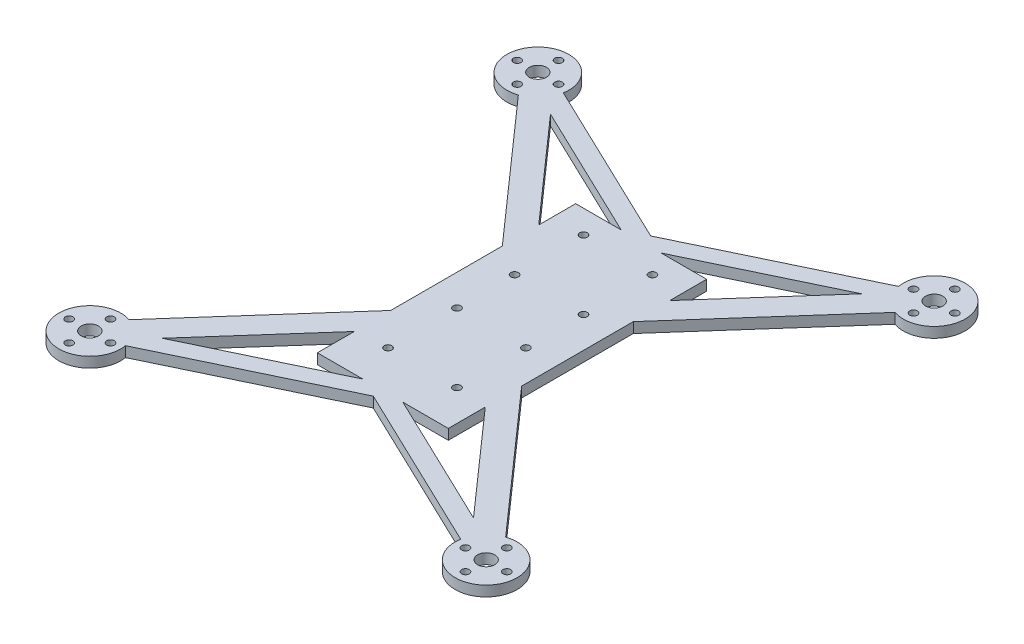
SolidWorks part; units mm, degrees
ref_plane "Front Plane" through (0, 0, 0) normal (0, 0, 1) x (1, 0, 0)
ref_plane "Top Plane" through (0, 0, 0) normal (0, 1, 0) x (1, 0, 0)
ref_plane "Right Plane" through (0, 0, 0) normal (1, 0, 0) x (0, 0, -1)
sketch "Sketch1" plane through (0, 0, 0) normal (0, 1, 0) x (1, 0, 0)
  line L0 (0, 37.475) -> (0, -37.475) construction
  line L1 (19, 37.475) -> (-19, 37.475)
  line L2 (19, 37.475) -> (19, -37.475)
  line L3 (19, -37.475) -> (-19, -37.475)
  line L4 (-19, 37.475) -> (-19, -37.475)
  line L5 (19, 37.475) -> (-19, -37.475) construction
  line L6 (19, -37.475) -> (-19, 37.475) construction
  line L7 (-19, 16.1958) -> (-54.6277, 56.4706)
  line L8 (57.5, -65) -> (-57.5, -65)
  line L9 (57.5, -65) -> (57.5, 65)
  line L10 (57.5, 65) -> (-57.5, 65)
  line L11 (-57.5, -65) -> (-57.5, 65)
  line L12 (57.5, -65) -> (-57.5, 65) construction
  line L13 (57.5, 65) -> (-57.5, -65) construction
  line L14 (-19, 16.1958) -> (-13.757, 20.8338)
  line L15 (-54.6277, 56.4706) -> (-49.3847, 61.1087)
  line L16 (-13.757, 20.8338) -> (-49.3847, 61.1087)
  line L17 (-19, 16.1958) -> (-49.3847, 61.1087) construction
  line L18 (-54.6277, 56.4706) -> (-13.757, 20.8338) construction
  line L19 (-57.5, 65) -> (0, 37.475) construction
  line L20 (-10, 30.75) -> (10, 30.75)
  line L21 (-10, 30.75) -> (-10, 10.75)
  line L22 (-10, 10.75) -> (10, 10.75)
  line L23 (10, 30.75) -> (10, 10.75)
  line L24 (-10, 30.75) -> (10, 10.75) construction
  line L25 (-10, 10.75) -> (10, 30.75) construction
  line L26 (-14.5, 5.525) -> (14.5, 5.525)
  line L27 (-14.5, 5.525) -> (-14.5, 35.975)
  line L28 (-14.5, 35.975) -> (14.5, 35.975)
  line L29 (14.5, 5.525) -> (14.5, 35.975)
  line L30 (-14.5, 5.525) -> (14.5, 35.975) construction
  line L31 (-14.5, 35.975) -> (14.5, 5.525) construction
  line L32 (-10, -5.975) -> (10, -5.975)
  line L33 (-10, -5.975) -> (-10, -25.975)
  line L34 (-10, -25.975) -> (10, -25.975)
  line L35 (10, -5.975) -> (10, -25.975)
  line L36 (-10, -5.975) -> (10, -25.975) construction
  line L37 (-10, -25.975) -> (10, -5.975) construction
  line L38 (-15.75, -35.975) -> (15.75, -35.975)
  line L39 (-15.75, -35.975) -> (-15.75, 4.025)
  line L40 (-15.75, 4.025) -> (15.75, 4.025)
  line L41 (15.75, -35.975) -> (15.75, 4.025)
  line L42 (-15.75, -35.975) -> (15.75, 4.025) construction
  line L43 (-15.75, 4.025) -> (15.75, -35.975) construction
  line L44 (-50.7811, 59.012) -> (3.6312, 32.9651)
  line L45 (-50.7811, 59.012) -> (-48.6222, 63.5219)
  line L46 (3.6312, 32.9651) -> (5.7901, 37.475)
  line L47 (-48.6222, 63.5219) -> (5.7901, 37.475)
  line L48 (-50.7811, 59.012) -> (5.7901, 37.475) construction
  line L49 (3.6312, 32.9651) -> (-48.6222, 63.5219) construction
  line L50 (50.7811, 59.012) -> (48.6222, 63.5219)
  line L51 (48.6222, 63.5219) -> (-5.7901, 37.475)
  line L52 (-3.6312, 32.9651) -> (-5.7901, 37.475)
  line L53 (50.7811, 59.012) -> (-3.6312, 32.9651)
  line L54 (19, 16.1958) -> (13.757, 20.8338)
  line L55 (13.757, 20.8338) -> (49.3847, 61.1087)
  line L56 (54.6277, 56.4706) -> (49.3847, 61.1087)
  line L57 (19, 16.1958) -> (54.6277, 56.4706)
  line L58 (-57.5, 0) -> (57.5, 0) construction
  line L64 (19, -16.1958) -> (13.757, -20.8338)
  line L65 (13.757, -20.8338) -> (49.3847, -61.1087)
  line L69 (50.7811, -59.012) -> (48.6222, -63.5219)
  line L70 (48.6222, -63.5219) -> (-5.7901, -37.475)
  line L71 (-3.6312, -32.9651) -> (-5.7901, -37.475)
  line L72 (50.7811, -59.012) -> (-3.6312, -32.9651)
  line L73 (-50.7811, -59.012) -> (-48.6222, -63.5219)
  line L74 (-48.6222, -63.5219) -> (5.7901, -37.475)
  line L75 (3.6312, -32.9651) -> (5.7901, -37.475)
  line L76 (-50.7811, -59.012) -> (3.6312, -32.9651)
  line L77 (54.6277, -56.4706) -> (49.3847, -61.1087)
  line L78 (19, -16.1958) -> (54.6277, -56.4706)
  line L79 (-19, -16.1958) -> (-13.757, -20.8338)
  line L80 (-13.757, -20.8338) -> (-49.3847, -61.1087)
  line L81 (-54.6277, -56.4706) -> (-49.3847, -61.1087)
  line L82 (-19, -16.1958) -> (-54.6277, -56.4706)
  circle A0 centre (-57.5, 65) radius 36
  circle A1 centre (-57.5, 65) radius 6
  circle A2 centre (-57.5, 65) radius 9
  circle A3 centre (-10, 30.75) radius 1.1
  circle A4 centre (10, 30.75) radius 1.1
  circle A5 centre (10, 10.75) radius 1.1
  circle A6 centre (-10, 10.75) radius 1.1
  circle A7 centre (-10, -5.975) radius 1.1
  circle A8 centre (10, -5.975) radius 1.1
  circle A9 centre (10, -25.975) radius 1.1
  circle A10 centre (-10, -25.975) radius 1.1
  circle A11 centre (-57.5, 71) radius 1.1
  circle A12 centre (-63.5, 65) radius 1.1
  circle A13 centre (-57.5, 59) radius 1.1
  circle A14 centre (-51.5, 65) radius 1.1
  circle A15 centre (57.5, 59) radius 1.1
  circle A16 centre (51.5, 65) radius 1.1
  circle A17 centre (57.5, 71) radius 1.1
  circle A18 centre (63.5, 65) radius 1.1
  circle A19 centre (57.5, 65) radius 9
  circle A20 centre (57.5, -65) radius 9
  circle A21 centre (51.5, -65) radius 1.1
  circle A22 centre (57.5, -59) radius 1.1
  circle A23 centre (63.5, -65) radius 1.1
  circle A24 centre (57.5, -71) radius 1.1
  circle A25 centre (-57.5, -59) radius 1.1
  circle A26 centre (-51.5, -65) radius 1.1
  circle A27 centre (-57.5, -71) radius 1.1
  circle A28 centre (-63.5, -65) radius 1.1
  circle A29 centre (-57.5, -65) radius 9
  circle A30 centre (-57.5, -65) radius 36
  circle A31 centre (57.5, 65) radius 36
  circle A32 centre (57.5, -65) radius 36
  circle A33 centre (-57.5, 65) radius 2.5
  circle A34 centre (57.5, 65) radius 2.5
  circle A35 centre (57.5, -65) radius 2.5
  circle A36 centre (-57.5, -65) radius 2.5
  point P0 (0, 0)
  point P8 (0, 0)
  point P16 (0, 20.75)
  point P18 (-34.1924, 38.6522)
  point P26 (0, 20.75)
  point P31 (0, -15.975)
  point P36 (0, -15.975)
  point P58 (-22.4955, 48.2435)
  point P103 (-34.1924, -38.6522)
  dimension "D3" = 72
  dimension "D4" = 12
  dimension "D5" = 3
  dimension "D17" = 2.2
  dimension "D19" = 5
  dimension "D2" = 1.5
  dimension "D6" = 115
  dimension "D7" = 130
  dimension "D8" = 3.25
  dimension "D9" = 7
  dimension "D10" = 20
  dimension "D11" = 29
  dimension "D12" = 30.45
  dimension "D13" = 40
  dimension "D14" = 31.5
  dimension "D15" = 1.5
  dimension "D16" = 1.5
  dimension "D18" = 5
extrude "Boss-Extrude1" add sketch "Sketch1" along normal blind 3 contours A2 | A11 | A14 | A13 | A12 | L7 L15 L16 L14 | L47 L46 L44 L45 | A19 | A15 | A18 | A17 | A16 | L57 L56 L55 L54 | L51 L52 L53 L50 | L1 L4 L3 L2 | A29 | A27 | A28 | A25 | A26 | L74 L75 L76 L73 | L80 L81 L82 L79 | A20 | A24 | A21 | A22 | A23 | L70 L71 L72 L69 | L65 L77 L78 L64 | A4 | A3 | A7 | A8 | A9 | A10 | A5 | A6 | A33 | A34 | A35 | A36
